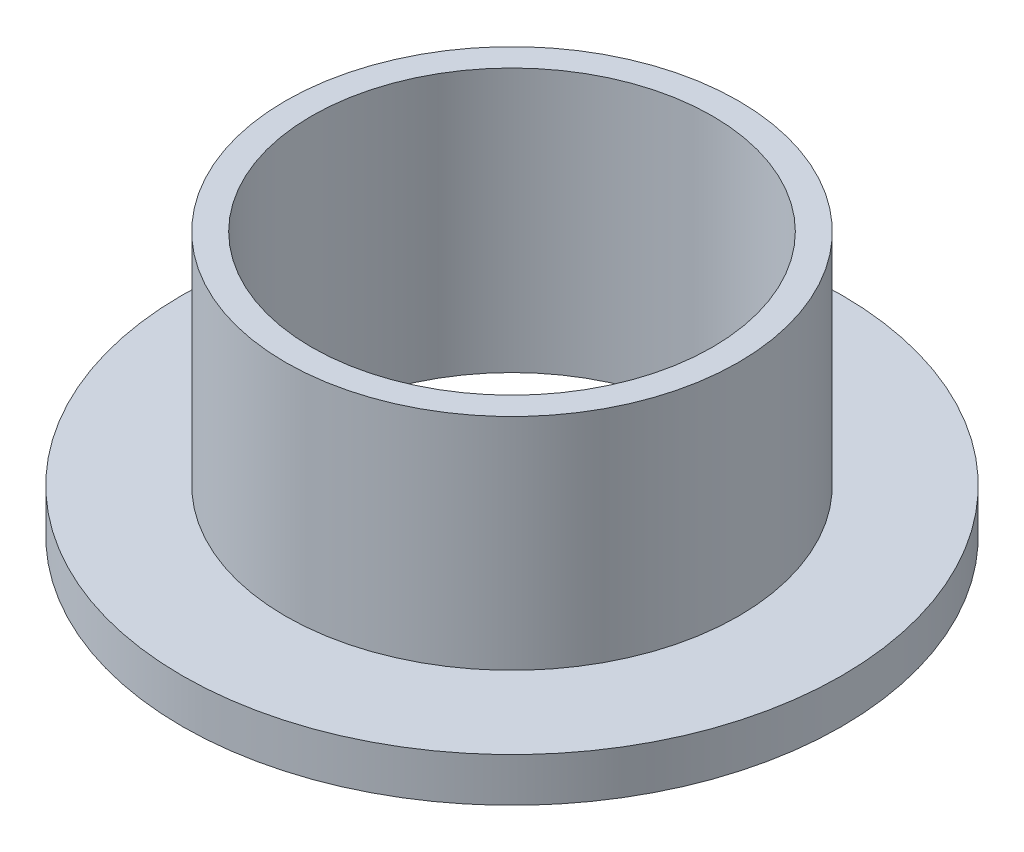
SolidWorks part; units mm, degrees
ref_plane "Front Plane" through (0, 0, 0) normal (0, 0, 1) x (1, 0, 0)
ref_plane "Top Plane" through (0, 0, 0) normal (0, 1, 0) x (1, 0, 0)
ref_plane "Right Plane" through (0, 0, 0) normal (1, 0, 0) x (0, 0, -1)
sketch "Sketch1" plane through (0, 0, 0) normal (0, 1, 0) x (1, 0, 0)
  circle A0 centre (0, 0) radius 20.6107
  circle A1 centre (0, 0) radius 30
  circle A2 centre (0, 0) radius 18.2318
  dimension "D1" = 60
extrude "Boss-Extrude1" add sketch "Sketch1" along normal blind 4 contours A1
extrude "Boss-Extrude2" add sketch "Sketch1<3>" along normal blind 24 contours A0
sketch "Sketch1<3>" plane through (0, 0, 0) normal (0, 1, 0) x (1, 0, 0) same geometry as "Sketch1"
extrude "Cut-Extrude1" cut sketch "Sketch1<6>" along normal through all contours A2 region at (0, 0, 0)
sketch "Sketch1<6>" plane through (0, 0, 0) normal (0, 1, 0) x (1, 0, 0) same geometry as "Sketch1"
